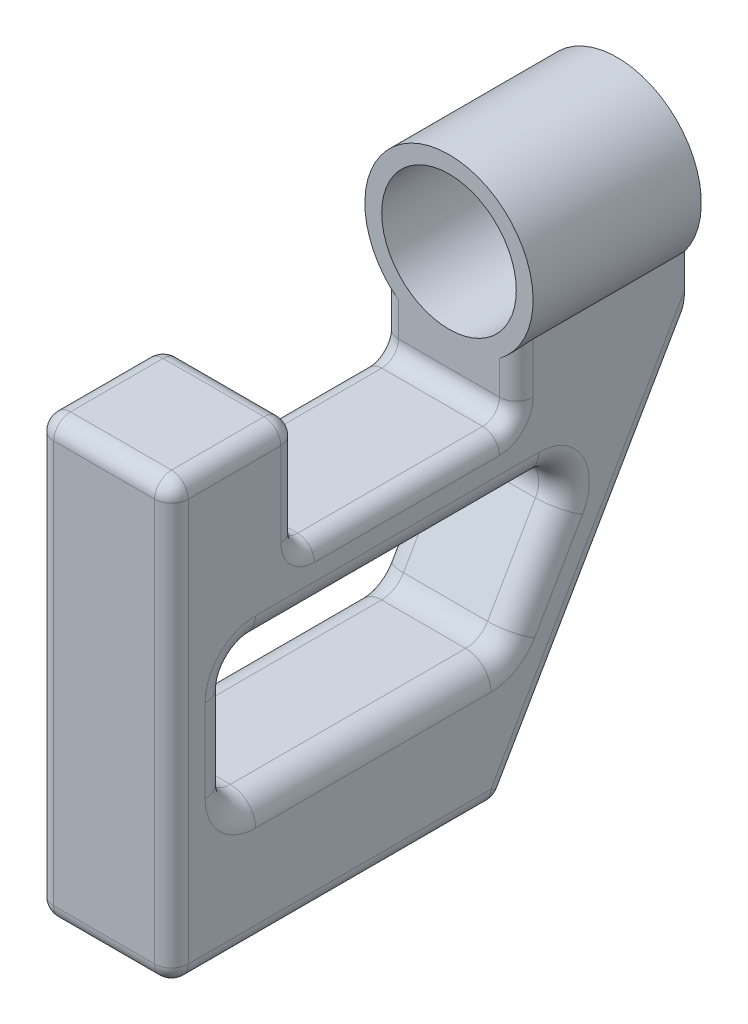
SolidWorks part; units mm, degrees
ref_plane "Piano frontale" through (0, 0, 0) normal (0, 0, 1) x (1, 0, 0)
ref_plane "Piano superiore" through (0, 0, 0) normal (0, 1, 0) x (1, 0, 0)
ref_plane "Piano destro" through (0, 0, 0) normal (1, 0, 0) x (0, 0, -1)
sketch "Schizzo1" plane through (0, 0, 0) normal (0, 0, 1) x (1, 0, 0)
  circle A1 centre (0, 0) radius 10
  dimension "D2" = 20
extrude "Estrusione-Estrusione1" add sketch "Schizzo1" along normal blind 20
sketch "Schizzo2" plane through (0, 0, 0) normal (1, 0, 0) x (0, 0, -1)
  line L0 (0, 0) -> (-20, 0)
  line L1 (-20, 0) -> (-20, -14)
  line L2 (-20, -14) -> (-46, -14)
  line L3 (-46, -14) -> (-46, 0)
  line L4 (-46, 0) -> (-61, 0)
  line L5 (-61, 0) -> (-61, -51.8622)
  line L6 (-61, -51.8622) -> (-21.8598, -51.8622)
  line L7 (0, -14) -> (0, 0)
  line L8 (-20, 10) -> (-20, -10) construction
  line L9 (0, -14) -> (-21.8598, -51.8622)
  dimension "D1" = 26
  dimension "D2" = 37.8622
  dimension "D3" = 14
  dimension "D5" = 15
  dimension "D6" = 60
extrude "Estrusione-Estrusione2" add sketch "Schizzo2" along normal blind 8 and the other way blind 8
sketch "Schizzo3" plane through (0, 0, 0) normal (0, 0, -1) x (-1, 0, 0)
  circle A0 centre (0, 0) radius 8
  dimension "D1" = 16
extrude "Taglio-Estrusione1" cut sketch "Schizzo3" against normal up to surface (20 mm away) up to face at (0, -6, 20)
sketch "Schizzo4" plane through (0, -51.8622, 0) normal (0, -1, 0) x (1, 0, 0)
  line L0 (0, 21.8598) -> (0, 61) construction
  line L2 (-8, 61) -> (8, 61) construction
  line L4 (-8, 21.8598) -> (8, 21.8598) construction
  circle A0 centre (0, 38) radius 3.75
  dimension "D1" = 7.5
  dimension "D2" = 23
extrude "Taglio-Estrusione2" cut sketch "Schizzo4" against normal blind 8
fillet "Raccordo1" radius 2 22 edges at (-8, -10, 20) (-8, -7, 46) (8, -10, 20) (8, -7, 46) (-8, -14, 33) (0, -14, 20) (8, -14, 33) (0, -14, 46) (-8, 0, 53.5) (0, 0, 46) (8, 0, 53.5) (0, 0, 61) (-8, -25.9311, 61) (8, -25.9311, 61) (-8, -51.8622, 41.4299) (0, -51.8622, 61) (8, -51.8622, 41.4299) (0, -51.8622, 34.25) (-8, -32.9311, 10.9299) (0, -51.8622, 21.8598) (8, -32.9311, 10.9299) (0, -14, 0)
sketch "Schizzo6" plane through (8, 0, 0) normal (1, 0, 0) x (0, 0, -1)
  line L0 (-54, -21) -> (-12.1244, -21)
  line L1 (-12.1244, -21) -> (-21.2824, -36.8622)
  line L2 (-21.2824, -36.8622) -> (-54, -36.8622)
  line L3 (-54, -36.8622) -> (-54, -21)
  line L5 (-44, -14) -> (-22, -14) construction
  line L7 (-41.75, -43.8622) -> (-34.25, -43.8622) construction
  line L8 (-61, -49.8622) -> (-61, -2) construction
  line L9 (-0.2679, -14.4641) -> (-21.2824, -50.8622) construction
  line L10 (-21.2824, -50.8622) -> (-0.2679, -14.4641) construction
  dimension "D1" = 7
  dimension "D2" = 7
  dimension "D3" = 7
  dimension "D4" = 7
extrude "Taglio-Estrusione4" cut sketch "Schizzo6" against normal up to next
fillet "Raccordo4" radius 3 12 edges at (8, -28.9311, 16.7034) (-8, -28.9311, 16.7034) (0, -36.8622, 21.2824) (8, -36.8622, 37.6412) (-8, -36.8622, 37.6412) (0, -36.8622, 54) (8, -28.9311, 54) (-8, -28.9311, 54) (0, -21, 54) (8, -21, 33.0622) (0, -21, 12.1244) (-8, -21, 33.0622)
